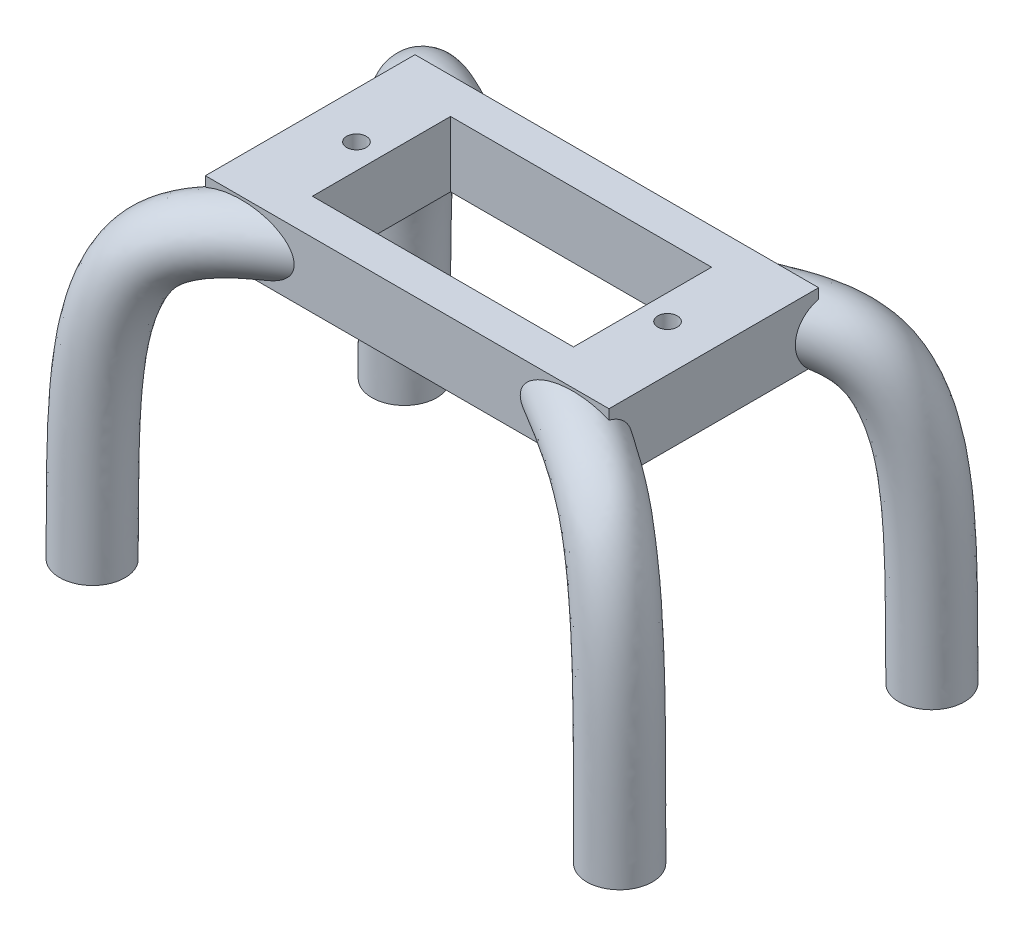
SolidWorks part; units mm, degrees
ref_plane "前视基准面" through (0, 0, 0) normal (0, 0, 1) x (1, 0, 0)
ref_plane "上视基准面" through (0, 0, 0) normal (0, 1, 0) x (1, 0, 0)
ref_plane "右视基准面" through (0, 0, 0) normal (1, 0, 0) x (0, 0, -1)
sketch "草图1" plane through (0, 0, 0) normal (0, 1, 0) x (1, 0, 0)
  line L0 (0, 0) -> (0, 12.535) construction
  line L1 (12, -6.35) -> (-12, -6.35)
  line L2 (12, -6.35) -> (12, 6.35)
  line L3 (12, 6.35) -> (-12, 6.35)
  line L4 (-12, -6.35) -> (-12, 6.35)
  line L5 (12, -6.35) -> (-12, 6.35) construction
  line L6 (12, 6.35) -> (-12, -6.35) construction
  line L7 (18.5533, -9.6358) -> (-18.5533, -9.6358)
  line L8 (18.5533, -9.6358) -> (18.5533, 9.6358)
  line L9 (18.5533, 9.6358) -> (-18.5533, 9.6358)
  line L10 (-18.5533, -9.6358) -> (-18.5533, 9.6358)
  line L11 (18.5533, -9.6358) -> (-18.5533, 9.6358) construction
  line L12 (18.5533, 9.6358) -> (-18.5533, -9.6358) construction
  line L13 (-14.3, 0) -> (0, 0) construction
  circle A0 centre (-14.3, 0) radius 0.9
  circle A2 centre (14.3, 0) radius 0.9
  point P0 (0, 0)
  point P6 (0, 0)
  dimension "D4" = 1.8
  dimension "D1" = 24
  dimension "D2" = 12.7
  dimension "D3" = 14.3
extrude "凸台-拉伸1" add sketch "草图1" along normal blind 6
ref_axis "基准轴1" through (0, 6.3, 0) along (0, -1, 0)
ref_plane "基准面2" through (0, 0, 0) normal (-0.5093, 0, 0.8606) x (0, -1, 0)
sketch "草图2" plane through (0, 0, 0) normal (0.5093, 0, -0.8606) x (-0.8606, 0, -0.5093)
  line L1 (20.8744, 6) -> (20.8744, 0) construction
  line L4 (0, 0) -> (0, 9.4521) construction
  line L5 (-13.5611, 6) -> (-13.5611, 0) construction
  line L6 (-13.5611, 6) -> (-13.5611, 0) construction
  line L7 (20.4583, 3) -> (-20.4583, 3) construction
  line L9 (0, 6.3) -> (0, -0.3) construction
  spline S0 degree 3 poles (-13.5611, 3) (-21.5757, 2.996) (-28.5203, -1.6821) (-28.1083, -14.5942) (-28.178, -25) knots 0 0 0 0 0.354063 1 1 1 1
  point P3 (20.8744, 3)
  dimension "D1" = 28.178
  dimension "D2" = 28
sweep "扫描1" add path "草图2" circular profile diameter 6 parameters "D3"=6
sketch "草图35" plane through (0.1453, -25.1877, 0.086) normal (0.0058, -1, 0.0034) x (1, 0.0058, 0)
  line L0 (-1153.5693, -682.642) -> (1153.6239, 682.6743) construction
  circle A0 centre (24.1054, 14.2647) radius 1.475
  dimension "D1" = 2.95
extrude "切除-拉伸1" cut sketch "草图35" against normal blind 6
mirror "镜向1" about plane through (0, 0, 0) normal (0, 0, 1) of "切除-拉伸1", "扫描1"
mirror "镜向2" about plane through (0, 0, 0) normal (1, 0, 0) of "镜向1"
